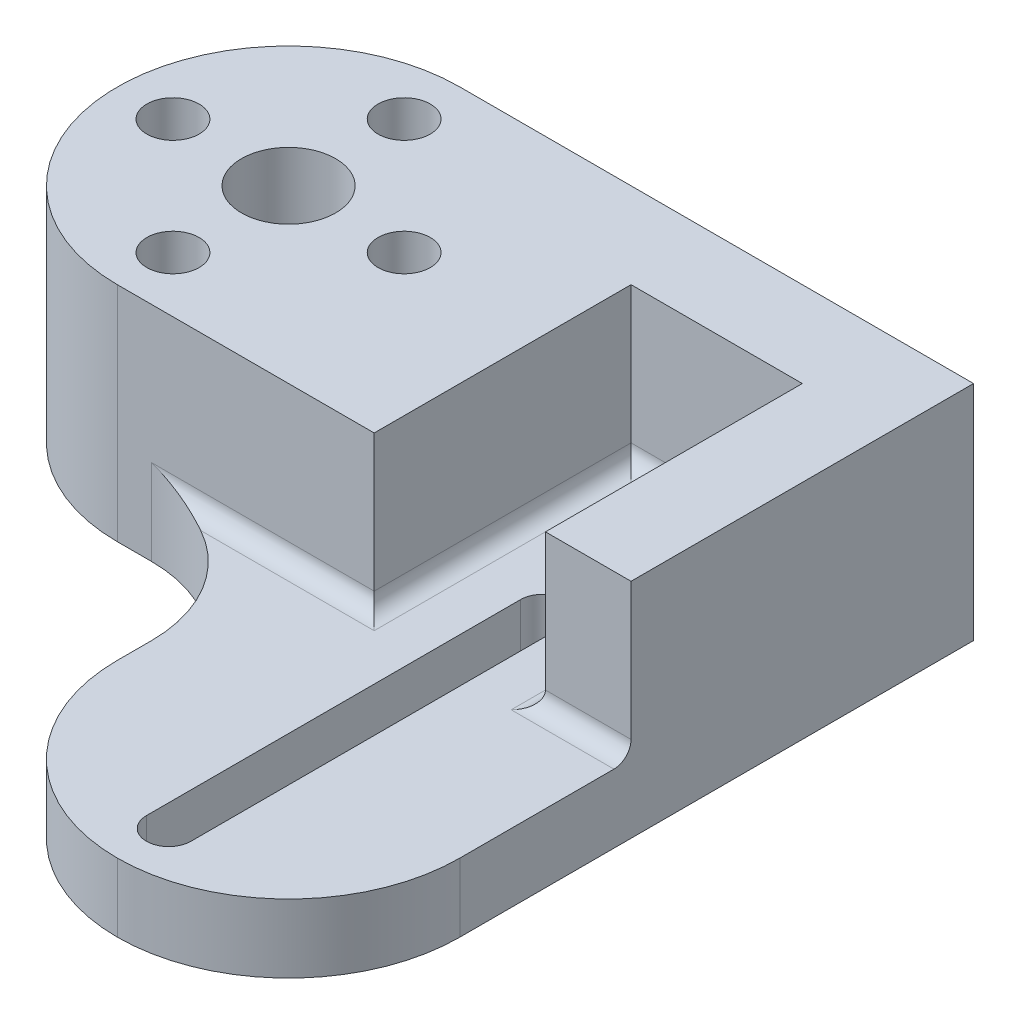
SolidWorks part; units mm, degrees
ref_plane "前视基准面" through (0, 0, 0) normal (0, 0, 1) x (1, 0, 0)
ref_plane "上视基准面" through (0, 0, 0) normal (0, 1, 0) x (1, 0, 0)
ref_plane "右视基准面" through (0, 0, 0) normal (1, 0, 0) x (0, 0, -1)
other "Configuration Table"
sketch "草图1" plane through (0, 0, 0) normal (0, 1, 0) x (1, 0, 0)
  line L0 (8.7, 4.8462) -> (8.7, -17)
  line L1 (0, 0) -> (-10, 0)
  line L3 (0, 20) -> (-10, 20)
  line L5 (0, 20) -> (20, 20)
  line L6 (0, 0) -> (0, -20)
  line L7 (0, -20) -> (20, -20)
  line L8 (20, 20) -> (20, -20)
  line L10 (11.3, -17) -> (11.3, 4.8462)
  line L11 (5, 15) -> (15, 15)
  line L12 (5, 15) -> (5, 0)
  line L13 (5, 0) -> (0, 0)
  line L14 (15, 15) -> (15, 0)
  line L15 (15, 0) -> (20, 0)
  arc A0 (-10, 20) -> (-10, 0) centre (-10, 10) ccw
  circle A1 centre (-10, 10) radius 2.75
  circle A2 centre (-10, 16.75) radius 1.525
  circle A3 centre (-3.25, 10) radius 1.525
  circle A4 centre (-10, 3.25) radius 1.525
  circle A5 centre (-16.75, 10) radius 1.525
  arc A6 (8.7, -17) -> (11.3, -17) centre (10, -17) ccw
  arc A7 (11.3, 4.8462) -> (8.7, 4.8462) centre (10, 4.8462) ccw
  dimension "D3" = 20
  dimension "D1" = 5.5
  dimension "D4" = 3.05
  dimension "D5" = 3.05
  dimension "D6" = 3.05
  dimension "D7" = 3.05
  dimension "D8" = 6.75
  dimension "D9" = 6.75
  dimension "D10" = 6.75
  dimension "D11" = 6.75
  dimension "D14" = 2.6
  dimension "D15" = 3
  dimension "D2" = 20
  dimension "D13" = 40
  dimension "D16" = 10
  dimension "D17" = 5
  dimension "D18" = 5
  dimension "D19" = 5
extrude "凸台-拉伸1" add sketch "草图1" along normal blind 13 contours L3 A0 L1 L13 L12 L11 L14 L15 L8 L5 A5 A4 A3 A2 A1 region at (-0.3747, 0, -10.6768)
extrude "凸台-拉伸2" add sketch "草图1<3>" along normal blind 4 contours L15 L14 L11 L12 L13 L6 L7 L8 A7 L10 A6 L0 region at (2.5, 0, 0.4031)
sketch "草图1<3>" plane through (0, 0, 0) normal (0, 1, 0) x (1, 0, 0) same geometry as "草图1"
fillet "圆角1" radius 8 1 edges at (0, 2, 0)
fillet "圆角2" radius 1 5 edges at (17.5, 4, 0) (15, 4, -7.5) (-1.5, 4, 0) (10, 4, -15) (5, 4, -7.5)
fillet "圆角3" radius 10 2 edges at (20, 2, 20) (0, 2, 20)
